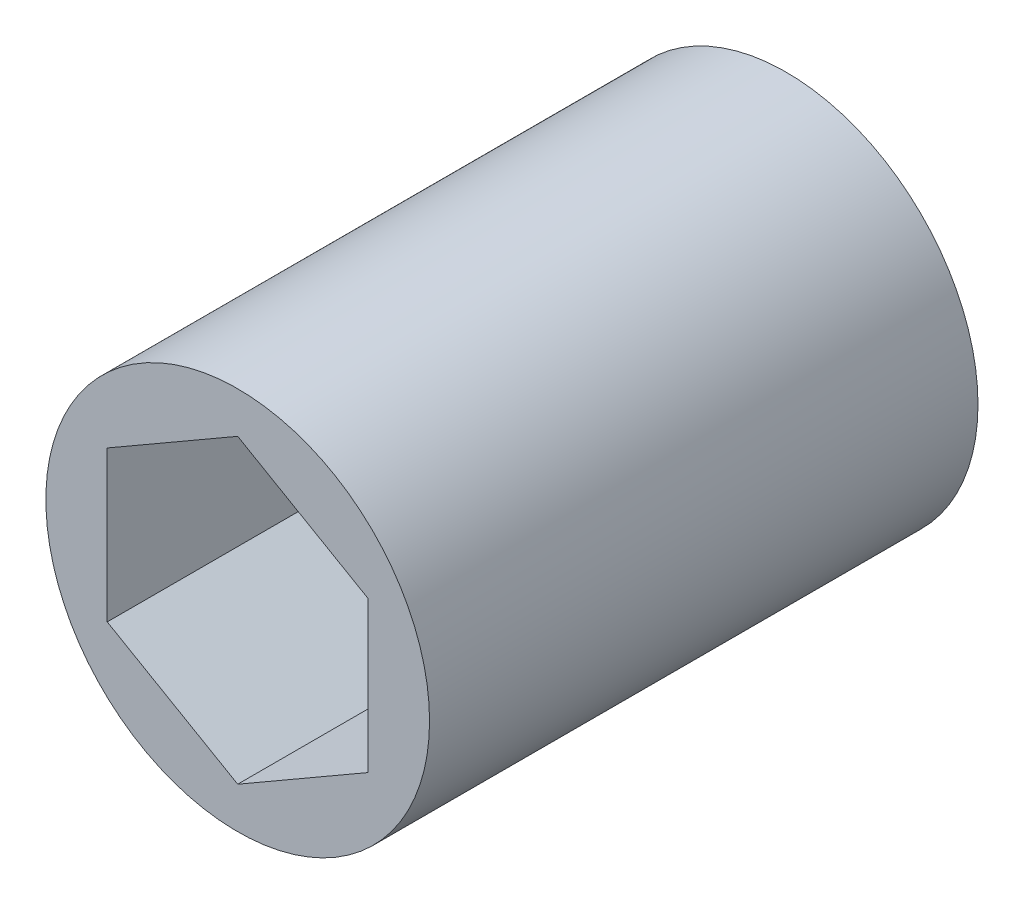
SolidWorks part; units mm, degrees
material "PET"
ref_plane "Front Plane" through (0, 0, 0) normal (0, 0, 1) x (1, 0, 0)
ref_plane "Top Plane" through (0, 0, 0) normal (0, 1, 0) x (1, 0, 0)
ref_plane "Right Plane" through (0, 0, 0) normal (1, 0, 0) x (0, 0, -1)
sketch "Sketch1" plane through (0, 0, 0) normal (0, 0, 1) x (1, 0, 0)
  line L1 (0, 7.479) -> (-6.477, 3.7395)
  line L2 (-6.477, 3.7395) -> (-6.477, -3.7395)
  line L3 (-6.477, -3.7395) -> (0, -7.479)
  line L4 (0, -7.479) -> (6.477, -3.7395)
  line L5 (6.477, -3.7395) -> (6.477, 3.7395)
  line L6 (6.477, 3.7395) -> (0, 7.479)
  circle A0 centre (0, 0) radius 9.525
  circle A1 centre (0, 0) radius 6.477 construction
  dimension "D1" = 12.954
  dimension "D2" = 19.05
extrude "Boss-Extrude1" add sketch "Sketch1" along normal mid plane 27.2288
